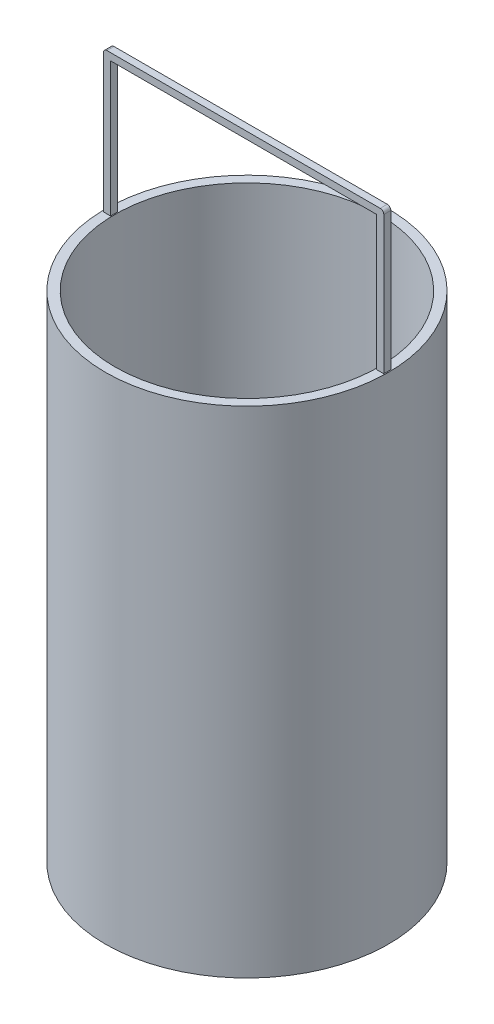
SolidWorks part; units mm, degrees
ref_plane "Plano frontal" through (0, 0, 0) normal (0, 0, 1) x (1, 0, 0)
ref_plane "Plano superior" through (0, 0, 0) normal (0, 1, 0) x (1, 0, 0)
ref_plane "Plano direito" through (0, 0, 0) normal (1, 0, 0) x (0, 0, -1)
sketch "Esboço1" plane through (0, 0, 0) normal (0, 1, 0) x (1, 0, 0)
  circle A0 centre (0, 0) radius 120
extrude "Ressalto-extrusão1" add sketch "Esboço1" along normal blind 200 and the other way blind 220
sketch "Esboço2" plane through (0, 200, 0) normal (0, 1, 0) x (1, 0, 0)
  circle A0 centre (0, 0) radius 112
extrude "Corte-extrusão1" cut sketch "Esboço2" against normal up to next
sketch "Esboço4" plane through (0, 0, 0) normal (0, 0, 1) x (1, 0, 0)
  line L0 (-118.7123, 200) -> (-118.7123, 320)
  line L1 (-118.7123, 320) -> (119.0454, 320)
  line L2 (119.0454, 320) -> (119.0454, 200)
  line L3 (119.0454, 200) -> (112, 200)
  line L4 (-112.7123, 200) -> (-112.7123, 314)
  line L5 (-112.7123, 314) -> (113.0454, 314)
  line L6 (113.0454, 314) -> (113.0454, 200)
  line L7 (-118.7123, 200) -> (-112.7123, 200)
  dimension "D1" = 6
extrude "Ressalto-extrusão3" add sketch "Esboço4" along normal blind 3 and the other way blind 3 contours L0 L7 L4 L5 L6 L3 L2 L1 region at (-116.049, 260, 0)
fillet "Filete2" radius 3 2 edges at (-118.7123, 320, 0) (119.0454, 320, 0)
